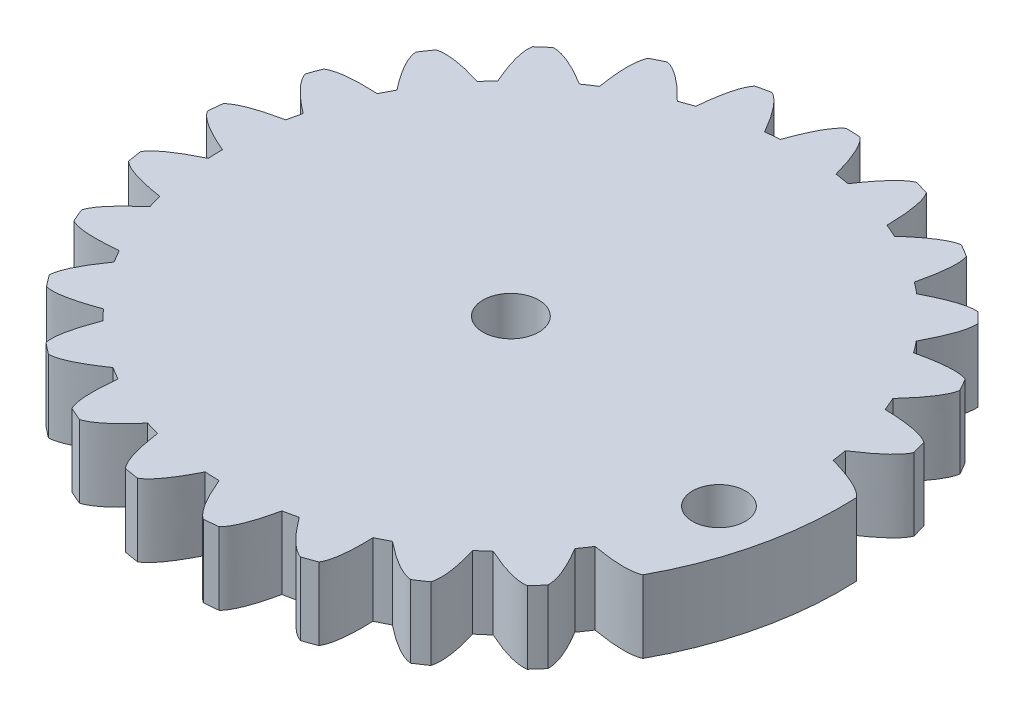
SolidWorks part; units mm, degrees
material "ABS"
ref_plane "Front Plane" through (0, 0, 0) normal (0, 0, 1) x (1, 0, 0)
ref_plane "Top Plane" through (0, 0, 0) normal (0, 1, 0) x (1, 0, 0)
ref_plane "Right Plane" through (0, 0, 0) normal (1, 0, 0) x (0, 0, -1)
sketch "Sketch1" plane through (0, 0, 0) normal (0, 1, 0) x (1, 0, 0)
  line L0 (12.6729, 15.3357) -> (15.4803, 12.4958) construction
  line L2 (14.0766, 13.9158) -> (16.2101, 16.0249) construction
  line L3 (16.2101, 16.0249) -> (16.3487, 16.1619)
  circle A0 centre (0, 0) radius 19.8944
  circle A1 centre (0, 0) radius 22.7939
  spline S0 degree 2 poles (15.4803, 12.4958) (18.6207, 18.4079) (12.6729, 15.3357) knots 0 0 0 1 1 1
  point P3 (12.6729, 15.3357)
  point P4 (15.4803, 12.4958)
  point P6 (15.8547, 16.3766)
  point P12 (11.8864, 15.9531)
  point P14 (16.3487, 16.1619)
  point P15 (16.5577, 15.6654)
  point P16 (8.4094, 18.0296)
  dimension "D1" = 39.7887
  dimension "D4" = 3
  dimension "D5" = 1
  dimension "D2" = 4
  dimension "D3" = 1
extrude "Boss-Extrude4" add sketch "Sketch1" along normal blind 5 contours A0 | A0 S0 A1 region at (14.994, 0, -14.8226) region at (0, 0, 0)
pattern_circular "CirPattern6" count 25 every 14.4 about axis through (0, 5, 0) along (0, 1, 0) of "Boss-Extrude4"
sketch "Sketch2" plane through (0, 5, 0) normal (0, 1, 0) x (1, 0, 0)
  circle A0 centre (0, 0) radius 1.925
  dimension "D1" = 3.85
extrude "Cut-Extrude2" cut sketch "Sketch2" against normal blind 10 contours A0 region at (0, 5, 0)
sketch "Sketch4" plane through (0, 0, 0) normal (0, -1, 0) x (1, 0, 0)
  circle A0 centre (18.5352, 4.177) radius 1.825
  dimension "D1" = 19
  dimension "D2" = 3.65
extrude "Cut-Extrude3" cut sketch "Sketch4" against normal blind 10
sketch "Sketch5" plane through (0, 5, 0) normal (0, 1, 0) x (1, 0, 0)
  line L0 (20.4744, -10.0181) -> (18.5012, -7.3137)
  line L1 (18.5012, -7.3137) -> (18.7663, -6.2305)
  line L2 (18.7663, -6.2305) -> (21.6262, -5.0336)
  line L3 (21.6262, -5.0336) -> (19.6135, -2.5127)
  line L4 (19.6135, -2.5127) -> (19.8386, -1.4879)
  line L5 (19.8386, -1.4879) -> (22.7938, 0.0851)
  arc A0 (20.4744, -10.0181) -> (22.7938, 0.0851) centre (0, 0) ccw
extrude "Boss-Extrude5" add sketch "Sketch5" against normal up to surface (5 mm away) up to face at (18.5352, 0, 2.352)
equation "\"number-of-teeth\"= 25"
equation "\"gear-size\"= 4mm"
equation "\"circumference\"= \"number-of-teeth\" * ( ( 1 + \"space-between-teeth\" ) * \"gear-size\" )"
equation "\"space-between-teeth\"= .25"
equation "\"D1@Sketch1\" = \"circumference\" / pi"
equation "\"D2@Sketch1\"=\"gear-size\""
equation "\"gear-length\"= 3mm"
equation "\"D4@Sketch1\"=\"gear-length\""
equation "\"D5@Sketch1\"=\"gear-size\" * \"space-between-teeth\""
equation "\"D3@Sketch1\"=\"gear-size\" * \"space-between-teeth\""
equation "\"D1@CirPattern6\"=\"number-of-teeth\""
equation "\"D2@CirPattern6\"=360 / \"number-of-teeth\""
